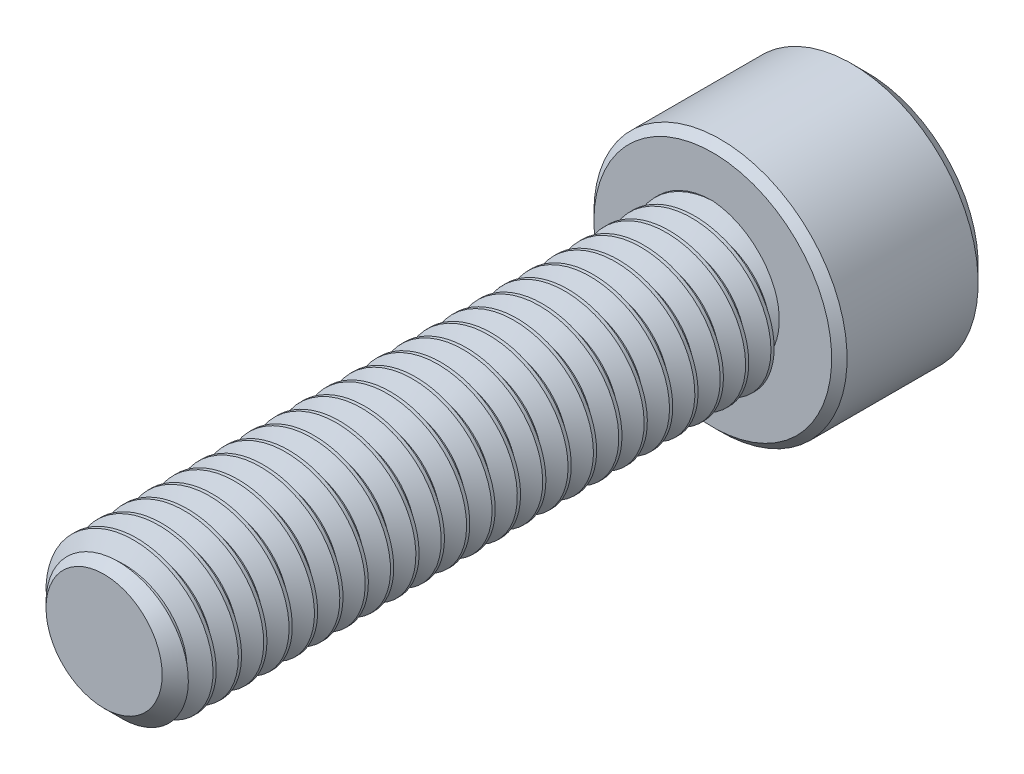
SolidWorks part; units mm, degrees
material "AISI 1020"
ref_plane "Front Plane" through (0, 0, 0) normal (0, 0, 1) x (1, 0, 0)
ref_plane "Top Plane" through (0, 0, 0) normal (0, 1, 0) x (1, 0, 0)
ref_plane "Right Plane" through (0, 0, 0) normal (1, 0, 0) x (0, 0, -1)
sketch "Sketch1" plane through (0, 0, 0) normal (0, 0, 1) x (1, 0, 0)
  line L0 (0, 2.413) -> (0, -2.413) construction
  circle A0 centre (0, 0) radius 2.413
  dimension "OD" = 4.826
extrude "Extrude1" add sketch "Sketch1" against normal blind 19.05
sketch "Sketch2" plane through (0, 0, 0) normal (0, 0, 1) x (1, 0, 0)
  circle A0 centre (0, 0) radius 2.413 construction
  circle A1 centre (0, 0) radius 2.413
curve "Helix/Spiral1" pitch 0.7937 height 19.8438 turns 25 parameters "pitch"=0.7937
chamfer "Chamfer3" distance 0.5953 angle 45 1 edges at (2.413, 0, 0)
sketch "Sketch3" plane through (0, 0, 0) normal (1, 0, 0) x (0, 0, -1)
  line L0 (-0.6945, 2.413) -> (-0.3969, 1.8974)
  line L1 (-0.3969, 1.8974) -> (-0.2977, 1.8974)
  line L2 (-0.2977, 1.8974) -> (0, 2.413)
  line L3 (-0.6945, 2.413) -> (0, 2.413)
  line L4 (-0.3473, 2.413) -> (-0.3473, 1.8974) construction
  line L5 (-0.5457, 2.1552) -> (-0.1488, 2.1552) construction
  line L6 (0, 2.413) -> (0, -2.413) construction
  dimension "D1" = 0.0992
  dimension "D2" = 0.3969
  dimension "D3" = 60
sweep "Cut-Sweep1" cut profiles "Sketch3" path "Helix/Spiral1"
sketch "Sketch6" plane through (0, 0, -19.05) normal (0, 0, -1) x (-1, 0, 0)
  circle A0 centre (0, 0) radius 3.9624
  dimension "head dia" = 7.9248
extrude "Extrude2" add sketch "Sketch6" along normal blind 4.826
sketch "Sketch7" plane through (0, 0, -23.876) normal (0, 0, -1) x (-1, 0, 0)
  line L1 (0, 2.2914) -> (-1.9844, 1.1457)
  line L2 (-1.9844, 1.1457) -> (-1.9844, -1.1457)
  line L3 (-1.9844, -1.1457) -> (0, -2.2914)
  line L4 (0, -2.2914) -> (1.9844, -1.1457)
  line L5 (1.9844, -1.1457) -> (1.9844, 1.1457)
  line L6 (1.9844, 1.1457) -> (0, 2.2914)
  circle A0 centre (0, 0) radius 1.9844 construction
  dimension "hex dia" = 3.9688
extrude "Cut-Extrude1" cut sketch "Sketch7" against normal blind 2.9766
sketch "Sketch8" plane through (0, 0, -23.876) normal (0, 0, -1) x (-1, 0, 0)
  circle A0 centre (0, 0) radius 2.2914
extrude "Cut-Extrude2" cut sketch "Sketch8" against normal blind 0.4826 draft 45
chamfer "Chamfer1" distance 0.4826 angle 45 1 edges at (-3.9624, 0, -23.876)
chamfer "Chamfer2" distance 0.2413 angle 45 1 edges at (-3.9624, 0, -19.05)
sketch "Sketch9" plane through (0, 0, 0) normal (1, 0, 0) x (0, 0, -1)
  line L0 (0, 2.413) -> (0, -2.413) construction
  line L1 (4.3656, 2.413) -> (4.3656, -2.413) construction
  line L2 (19.05, 3.9624) -> (19.05, -3.9624) construction
  line L3 (23.876, 3.9624) -> (23.876, -3.9624) construction
  line L4 (23.876, 0) -> (0, 0) construction
  dimension "D1" = 4.3656
  dimension "D2" = 4.826
  dimension "D3" = 7.9248
  dimension "D4" = 19.05
equation "\"D3@Helix/Spiral1\" = \"screw length@Extrude1\"+\"pitch@Helix/Spiral1\""
equation "\"D1@Sketch3\" = \"pitch@Helix/Spiral1\"*.125"
equation "\"D2@Sketch3\" = \"pitch@Helix/Spiral1\"*.5"
equation "\"D1@Cut-Extrude1\" = \"hex dia@Sketch7\"*.75"
equation "\"D1@Chamfer1\" = \"head depth@Extrude2\"/10"
equation "\"D1@Sketch9\" = \"pitch@Helix/Spiral1\"*5.5"
equation "\"D1@Chamfer2\" = \"D1@Chamfer1\"/2"
equation "\"D1@Cut-Extrude2\" = \"D1@Chamfer2\"*2"
equation "\"D1@Chamfer3\" = \"pitch@Helix/Spiral1\"*.750"
equation "\"D2@Sketch9\" = \"head depth@Extrude2\""
equation "\"D3@Sketch9\" = \"head dia@Sketch6\""
equation "\"D4@Sketch9\" = \"screw length@Extrude1\""
